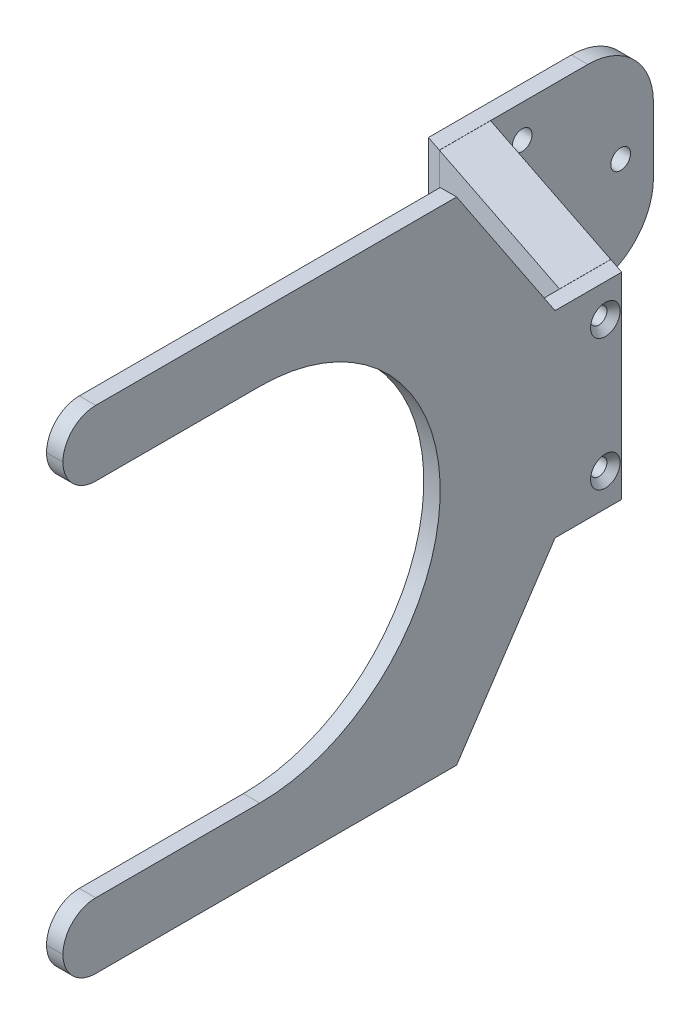
SolidWorks part; units mm, degrees
ref_plane "Front Plane" through (0, 0, 0) normal (0, 0, 1) x (1, 0, 0)
ref_plane "Top Plane" through (0, 0, 0) normal (0, 1, 0) x (1, 0, 0)
ref_plane "Right Plane" through (0, 0, 0) normal (1, 0, 0) x (0, 0, -1)
sketch "Sketch1" plane through (0, 0, 0) normal (0, 1, 0) x (1, 0, 0)
  line L0 (0, 0) -> (0, -38.1)
  line L1 (0, -38.1) -> (38.1, -50.8)
  line L2 (38.1, -50.8) -> (38.1, -152.4)
  line L3 (34.925, -152.4) -> (34.925, -53.0884)
  line L4 (34.925, -53.0884) -> (-3.175, -40.3884)
  line L5 (-3.175, -40.3884) -> (-3.175, 0)
  line L6 (-3.175, 0) -> (0, 0)
  line L7 (34.925, -152.4) -> (38.1, -152.4)
  dimension "D1" = 101.6
  dimension "D2" = 38.1
  dimension "D3" = 12.7
  dimension "D4" = 38.1
  dimension "D5" = 3.175
  dimension "D6" = 3.175
  dimension "D7" = 3.175
extrude "Boss-Extrude1" add sketch "Sketch1" along normal mid plane 95.25
sketch "Sketch2" plane through (38.1, 0, 0) normal (1, 0, 0) x (0, 0, -1)
  line L0 (-114.3, 34.925) -> (-152.4, 34.925)
  line L1 (-152.4, 47.625) -> (-152.4, -47.625) construction
  line L2 (-152.4, 34.925) -> (-152.4, -34.925)
  line L3 (-152.4, -34.925) -> (-114.3, -34.925)
  line L4 (-50.8, 47.625) -> (-50.8, -47.625) construction
  line L5 (0, 19.05) -> (-57.15, 19.05)
  line L6 (0, 47.625) -> (0, -47.625) construction
  line L7 (-57.15, 19.05) -> (-76.2, 47.625)
  line L8 (-152.4, 47.625) -> (-50.8, 47.625) construction
  line L9 (-76.2, 47.625) -> (0, 47.625)
  line L10 (0, 47.625) -> (0, 19.05)
  line L11 (0, 0) -> (-114.3, 0) construction
  line L12 (0, -47.625) -> (0, -19.05)
  line L13 (-76.2, -47.625) -> (0, -47.625)
  line L14 (-57.15, -19.05) -> (-76.2, -47.625)
  line L15 (0, -19.05) -> (-57.15, -19.05)
  arc A0 (-114.3, -34.925) -> (-114.3, 34.925) centre (-114.3, 0) ccw
  point P9 (-152.4, 0)
  point P12 (-50.8, 0)
  dimension "D1" = 69.85
  dimension "D2" = 38.1
  dimension "D3" = 57.15
  dimension "D4" = 76.2
  dimension "D5" = 19.05
extrude "Cut-Extrude1" cut sketch "Sketch2" against normal through all
fillet "Fillet1" radius 6.35 4 edges at (36.5125, -47.625, 152.4) (36.5125, -34.925, 152.4) (36.5125, 47.625, 152.4) (36.5125, 34.925, 152.4)
fillet "Fillet2" radius 12.7 2 edges at (-1.5875, -19.05, 0) (-1.5875, 19.05, 0)
sketch "Sketch3" plane through (0, 0, 0) normal (1, 0, 0) x (0, 0, -1)
  circle A0 centre (-25.4, 12.7) radius 1.905
  circle A1 centre (-6.35, 0) radius 1.905
  circle A2 centre (-25.4, -12.7) radius 1.905
  dimension "D1" = 3.81
  dimension "D2" = 3.81
  dimension "D3" = 3.81
  dimension "D4" = 25.4
  dimension "D5" = 12.7
  dimension "D6" = 19.05
  dimension "D7" = 6.35
extrude "Cut-Extrude2" cut sketch "Sketch3" against normal up to next
sketch "Sketch5" plane through (0, 19.05, 0) normal (0, 1, 0) x (1, 0, 0)
  line L0 (38.1, -50.8) -> (38.1, -44.2404)
  line L1 (38.1, -44.2404) -> (0, -31.5404)
  line L2 (0, -12.7) -> (0, -38.1) construction
  line L3 (0, -31.5404) -> (0, -38.1)
  line L4 (0, -38.1) -> (38.1, -50.8)
  line L5 (34.925, -53.0884) -> (-3.175, -40.3884) construction
  dimension "D1" = 9.398
extrude "Boss-Extrude2" add sketch "Sketch5" against normal up to surface (38.1 mm away) up to face at (17.4625, -19.05, 40.2596)
sketch "Sketch6" plane through (0, 19.05, 0) normal (0, 1, 0) x (1, 0, 0)
  line L1 (34.925, -53.0884) -> (34.8996, -53.0884)
  line L2 (34.925, -53.0884) -> (34.925, -40.401)
  line L3 (34.925, -40.401) -> (34.8996, -40.401)
  line L4 (34.8996, -53.0884) -> (34.8996, -40.401)
  line L5 (0, -31.5404) -> (0.0254, -31.5404)
  line L6 (0, -31.5404) -> (0, -48.6593)
  line L7 (0, -48.6593) -> (0.0254, -48.6593)
  line L8 (0.0254, -31.5404) -> (0.0254, -48.6593)
  dimension "D1" = 0.0254
  dimension "D2" = 0.0254
extrude "Cut-Extrude3" cut sketch "Sketch6" against normal through all
sketch "Sketch7" plane through (38.1, 0, 0) normal (1, 0, 0) x (0, 0, -1)
  line L1 (-57.15, 19.05) -> (-44.2404, 19.05) construction
  line L2 (-44.2404, -19.05) -> (-44.2404, 19.05) construction
  circle A0 centre (-47.4154, 12.7) radius 1.5875
  circle A1 centre (-47.4154, -12.7) radius 1.5875
  dimension "D1" = 3.175
  dimension "D2" = 3.175
  dimension "D4" = 6.35
  dimension "D5" = 3.175
  dimension "D3" = 25.4
extrude "Cut-Extrude4" cut sketch "Sketch7" against normal blind 3.175
sketch "Sketch8" plane through (34.8996, 0, 0) normal (1, 0, 0) x (0, 0, -1)
  circle A0 centre (-47.4154, 12.7) radius 1.27
  circle A1 centre (-47.4154, -12.7) radius 1.27
  dimension "D1" = 2.54
  dimension "D2" = 2.54
extrude "Cut-Extrude5" cut sketch "Sketch8" against normal blind 6.35
sketch "Sketch9" plane through (-3.175, 0, 0) normal (-1, 0, 0) x (0, 0, 1)
  line L0 (40.3884, 19.05) -> (12.7, 19.05) construction
  line L1 (40.3884, 19.05) -> (40.3884, -19.05) construction
  circle A0 centre (37.2134, 12.7) radius 1.5875
  circle A1 centre (37.2134, -12.7) radius 1.5875
  dimension "D4" = 3.175
  dimension "D5" = 3.175
  dimension "D1" = 25.4
  dimension "D2" = 6.35
  dimension "D3" = 3.175
extrude "Cut-Extrude6" cut sketch "Sketch9" against normal blind 3.175
sketch "Sketch10" plane through (0.0254, 0, 0) normal (-1, 0, 0) x (0, 0, 1)
  circle A0 centre (37.2134, 12.7) radius 1.27
  circle A1 centre (37.2134, -12.7) radius 1.27
  dimension "D1" = 2.54
  dimension "D2" = 2.54
extrude "Cut-Extrude7" cut sketch "Sketch10" against normal blind 6.35
chamfer "Chamfer1" distance 1.27 angle 45 2 edges at (38.1, 12.7, 45.8279) (38.1, -12.7, 45.8279)
chamfer "Chamfer2" distance 1.27 angle 45 2 edges at (-3.175, -12.7, 38.8009) (-3.175, 12.7, 38.8009)
